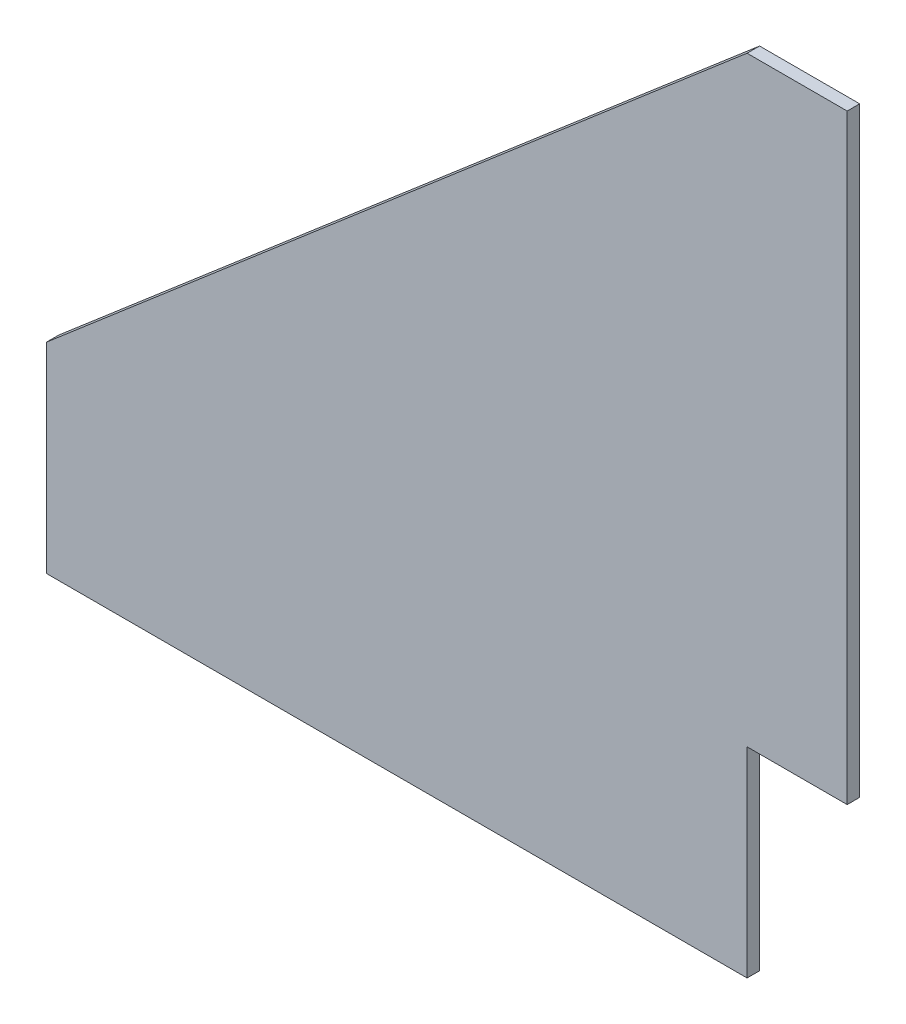
SolidWorks part; units mm, degrees
ref_plane "Front Plane" through (0, 0, 0) normal (0, 0, 1) x (1, 0, 0)
ref_plane "Top Plane" through (0, 0, 0) normal (0, 1, 0) x (1, 0, 0)
ref_plane "Right Plane" through (0, 0, 0) normal (1, 0, 0) x (0, 0, -1)
sketch "Sketch1" plane through (0, 0, 0) normal (0, 0, 1) x (1, 0, 0)
  line L0 (0, 0) -> (0, 152.4)
  line L1 (0, 152.4) -> (-25.4, 152.4)
  line L3 (-203.2, -50.8) -> (-25.4, -50.8)
  line L4 (-25.4, -50.8) -> (-25.4, 0)
  line L5 (-25.4, 0) -> (0, 0)
  line L6 (-203.2, -50.8) -> (-203.2, 0)
  line L7 (-203.2, 0) -> (-25.4, 152.4)
  dimension "D1" = 152.4
  dimension "D2" = 177.8
  dimension "D3" = 25.4
  dimension "D4" = 50.8
  dimension "D5" = 25.4
  dimension "D6" = 50.8
extrude "Boss-Extrude1" add sketch "Sketch1" along normal blind 3.175
